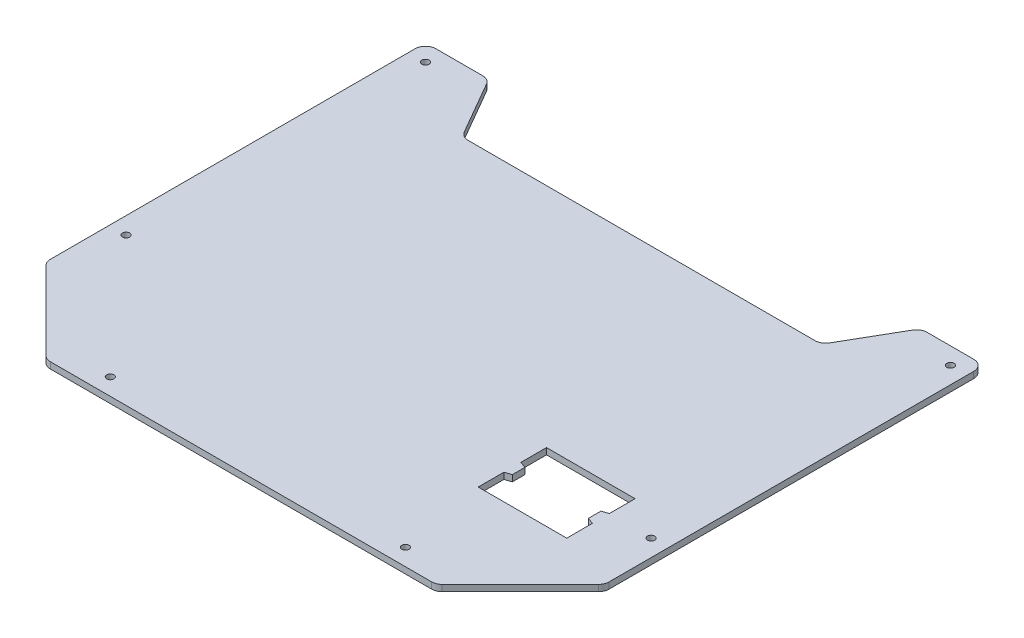
SolidWorks part; units mm, degrees
material "Acier non allié"
ref_plane "Front" through (0, 0, 0) normal (0, 0, 1) x (1, 0, 0)
ref_plane "Top" through (0, 0, 0) normal (0, 1, 0) x (1, 0, 0)
ref_plane "Right" through (0, 0, 0) normal (1, 0, 0) x (0, 0, -1)
sketch "Esquisse1" plane through (0, 0, 0) normal (0, 1, 0) x (1, 0, 0)
  line L0 (0, 0) -> (0, 1919.0564) construction
  line L1 (-92.5, 0) -> (92.5, 0)
  line L2 (92.5, 0) -> (132.5, 40)
  line L3 (132.5, 40) -> (132.5, 220)
  line L4 (132.5, 220) -> (102.5, 220)
  line L5 (102.5, 220) -> (85.1795, 190)
  line L6 (85.1795, 190) -> (-85.1795, 190)
  line L7 (-102.5, 220) -> (-85.1795, 190)
  line L8 (-132.5, 220) -> (-102.5, 220)
  line L9 (-132.5, 40) -> (-132.5, 220)
  line L10 (-92.5, 0) -> (-132.5, 40)
  point P12 (0, 190)
  dimension "D1" = 132.5
  dimension "D2" = 220
  dimension "D3" = 30
  dimension "D4" = 30
  dimension "D5" = 40
  dimension "D6" = 40
  dimension "D7" = 60
extrude "Boss.-Extru.1" add sketch "Esquisse1" along normal blind 3
fillet "Congé1" radius 5 10 edges at (132.5, 1.5, -220) (102.5, 1.5, -220) (85.1795, 1.5, -190) (-85.1795, 1.5, -190) (-102.5, 1.5, -220) (-132.5, 1.5, -220) (-132.5, 1.5, -40) (-92.5, 1.5, 0) (92.5, 1.5, 0) (132.5, 1.5, -40)
sketch "Esquisse2" plane through (0, 0, 0) normal (0, -1, 0) x (1, 0, 0)
  line L0 (0, 0) -> (0, -330.9968) construction
  line L1 (-90.4289, 0) -> (90.4289, 0) construction
  line L2 (-105.3868, -220) -> (-127.5, -220) construction
  line L3 (-132.5, -215) -> (-132.5, -42.0711) construction
  circle A0 centre (-70, -8) radius 1
  circle A1 centre (-124.5, -70) radius 1
  circle A2 centre (-124.5, -212) radius 1
  circle A3 centre (124.5, -212) radius 1
  circle A4 centre (124.5, -70) radius 1
  circle A5 centre (70, -8) radius 1
  dimension "D3" = 2
  dimension "D6" = 2
  dimension "D9" = 2
  dimension "D1" = 70
  dimension "D2" = 8
  dimension "D4" = 124.5
  dimension "D5" = 70
  dimension "D7" = 8
  dimension "D8" = 8
extrude "Enlèv. mat.-Extru.1" cut sketch "Esquisse2" against normal through all
hole_wizard "Dégagement M31" positions "Esquisse3" profile "Esquisse4" hole size "M3" standard "ISO" end condition through all
sketch "Esquisse3" plane through (0, 0, 0) normal (0, -1, 0) x (-1, 0, 0)
  point P0 (-70, 8)
  point P3 (-124.5, 70)
  point P6 (-124.5, 212)
  point P9 (124.5, 212)
  point P12 (124.5, 70)
  point P15 (70, 8)
sketch "Esquisse4" plane through (70, 0, -8) normal (1, 0, 0) x (0, 0, -1)
  line L0 (0, 0) -> (0, 3)
  line L1 (0, 3) -> (1.7, 3)
  line L2 (1.7, 3) -> (1.7, 0)
  line L5 (1.7, 0) -> (0, 0)
  line L11 (0, -6.35) -> (0, 107.95) construction
  dimension "Diamètre du perçage jusqu'au prochain" = 3.4
  dimension "Profondeur du perçage jusqu'au prochain" = 3
sketch "Esquisse5" plane through (0, 0, 0) normal (0, -1, 0) x (1, 0, 0)
  line L0 (132.5, -42.0711) -> (132.5, -215) construction
  line L1 (104.5, -82.4) -> (62.5, -82.4) construction
  line L2 (104.5, -82.4) -> (104.5, -50) construction
  line L3 (104.5, -50) -> (62.5, -50) construction
  line L4 (62.5, -82.4) -> (62.5, -50) construction
  line L5 (-90.4289, 0) -> (90.4289, 0) construction
  line L6 (83.5, -82.4) -> (83.5, -41.1293) construction
  line L7 (104.5, -66.2) -> (27.496, -66.2) construction
  line L8 (104.5, -50) -> (62.5, -50)
  line L9 (62.5, -50) -> (62.5, -62.2)
  line L10 (62.5, -62.2) -> (65.5, -63.2)
  line L11 (65.5, -63.2) -> (65.5, -69.2)
  line L12 (101.5, -63.2) -> (101.5, -69.2)
  line L13 (104.5, -62.2) -> (101.5, -63.2)
  line L14 (104.5, -50) -> (104.5, -62.2)
  line L15 (62.5, -70.2) -> (65.5, -69.2)
  line L16 (62.5, -82.4) -> (62.5, -70.2)
  line L17 (104.5, -82.4) -> (62.5, -82.4)
  line L18 (104.5, -70.2) -> (101.5, -69.2)
  line L19 (104.5, -82.4) -> (104.5, -70.2)
  point P19 (83.5, -50)
  point P21 (65.5, -66.2)
  point P23 (101.5, -66.2)
  dimension "D1" = 32.4
  dimension "D2" = 42
  dimension "D3" = 28
  dimension "D4" = 50
  dimension "D5" = 3
  dimension "D6" = 3
  dimension "D7" = 4
extrude "Enlèv. mat.-Extru.2" cut sketch "Esquisse5" against normal through all
equation "\"WIDTH\"= 300mm'Total width of the robot"
equation "\"LENGTH\"= 220mm'Total length of the robot"
equation "\"CUT_DEPTH\"= 45mm'Depth of the cut on the edges of the plate"
equation "\"Plate_th\"= 3mm'Thickness of the plate"
equation "\"D1\"= \"Plate_th\""
